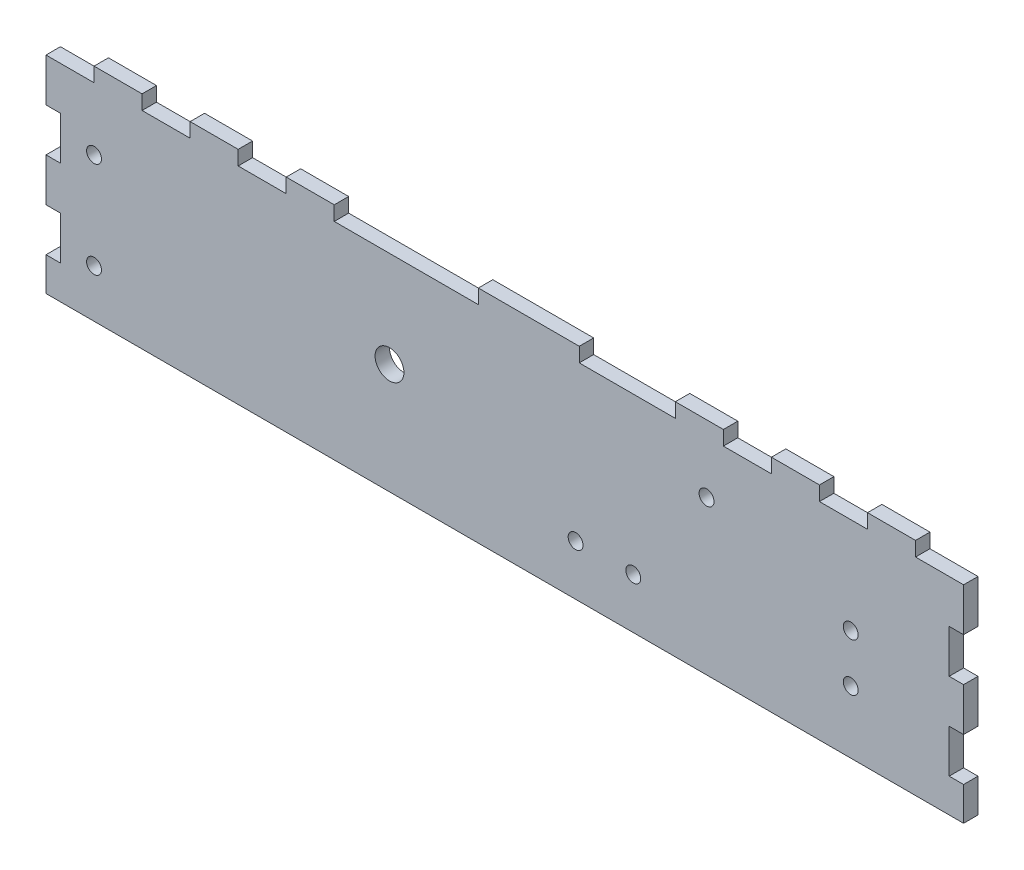
SolidWorks part; units mm, degrees
ref_plane "Front Plane" through (0, 0, 0) normal (0, 0, 1) x (1, 0, 0)
ref_plane "Top Plane" through (0, 0, 0) normal (0, 1, 0) x (1, 0, 0)
ref_plane "Right Plane" through (0, 0, 0) normal (1, 0, 0) x (0, 0, -1)
sketch "Sketch1" plane through (0, 0, 0) normal (0, 0, 1) x (1, 0, 0)
  line L4 (-191, 0) -> (0, 0)
  line L5 (0, 0) -> (0, 46)
  line L6 (0, 46) -> (-191, 46)
  line L7 (-191, 46) -> (-191, 0)
  line L8 (-191, 0) -> (0, 0)
  line L9 (0, 0) -> (0, 46)
  line L10 (0, 46) -> (-191, 46)
  line L11 (-191, 46) -> (-191, 0)
  circle A0 centre (-181, 30) radius 1.55 construction
  circle A1 centre (-181, 10) radius 1.55 construction
  circle A2 centre (-181, 30) radius 1.55
  circle A3 centre (-181, 10) radius 1.55
  dimension "D1" = 0
extrude "Boss-Extrude1" add sketch "Sketch1" along normal blind 3
sketch "Sketch5" plane through (0, 0, 3) normal (0, 0, 1) x (1, 0, 0)
  line L0 (-95.5, 0) -> (-95.5, 46) construction
  line L1 (-191, 0) -> (0, 0) construction
  line L2 (0, 46) -> (-191, 46) construction
ref_axis "Axis1" through (-95.5, 0, 3) along (0, 1, 0)
ref_plane "Plane1" through (-95.5, 0, 0) normal (1, 0, 0) x (0, 1, 0)
sketch "Sketch2" plane through (0, 0, 3) normal (0, 0, 1) x (1, 0, 0)
  line L0 (-119.5, 46) -> (-119.5, 0) construction
  line L1 (-119.5, 46) -> (-119.5, 0)
  point P2 (-119.5, 23)
ref_point "MointPoint-Sus"
sketch "Sketch3" plane through (0, 0, 0) normal (0, 0, -1) x (-1, 0, 0)
  line L4 (50, 43) -> (50, 46)
  line L5 (50, 46) -> (40, 46)
  line L6 (40, 46) -> (40, 43)
  line L7 (40, 43) -> (50, 43)
  line L8 (50, 43) -> (50, 46)
  line L9 (50, 46) -> (40, 46)
  line L10 (40, 46) -> (40, 43)
  line L11 (40, 43) -> (50, 43)
  line L12 (30, 43) -> (30, 46)
  line L13 (30, 46) -> (20, 46)
  line L14 (20, 46) -> (20, 43)
  line L15 (20, 43) -> (30, 43)
  line L16 (30, 43) -> (30, 46)
  line L17 (30, 46) -> (20, 46)
  line L18 (20, 46) -> (20, 43)
  line L19 (20, 43) -> (30, 43)
  line L20 (10, 43) -> (10, 46)
  line L21 (10, 46) -> (0, 46)
  line L22 (0, 46) -> (0, 43)
  line L23 (0, 43) -> (10, 43)
  line L24 (10, 43) -> (10, 46)
  line L25 (10, 46) -> (0, 46)
  line L26 (0, 46) -> (0, 43)
  line L27 (0, 43) -> (10, 43)
  line L28 (171, 43) -> (171, 46)
  line L29 (171, 46) -> (161, 46)
  line L30 (161, 46) -> (161, 43)
  line L31 (161, 43) -> (171, 43)
  line L32 (171, 43) -> (171, 46)
  line L33 (171, 46) -> (161, 46)
  line L34 (161, 46) -> (161, 43)
  line L35 (161, 43) -> (171, 43)
  line L36 (151, 43) -> (151, 46)
  line L37 (151, 46) -> (141, 46)
  line L38 (141, 46) -> (141, 43)
  line L39 (141, 43) -> (151, 43)
  line L40 (151, 43) -> (151, 46)
  line L41 (151, 46) -> (141, 46)
  line L42 (141, 46) -> (141, 43)
  line L43 (141, 43) -> (151, 43)
  line L44 (131, 46) -> (101, 46)
  line L45 (101, 46) -> (101, 43)
  line L46 (101, 43) -> (131, 43)
  line L47 (131, 43) -> (131, 46)
  line L48 (131, 46) -> (101, 46)
  line L49 (101, 46) -> (101, 43)
  line L50 (101, 43) -> (131, 43)
  line L51 (131, 43) -> (131, 46)
  line L52 (80, 46) -> (60, 46)
  line L53 (80, 43) -> (80, 46)
  line L54 (60, 43) -> (80, 43)
  line L55 (60, 46) -> (60, 43)
  line L56 (80, 46) -> (60, 46)
  line L57 (80, 43) -> (80, 46)
  line L58 (60, 43) -> (80, 43)
  line L59 (60, 46) -> (60, 43)
  line L60 (181, 43) -> (191, 43)
  line L61 (181, 46) -> (181, 43)
  line L62 (191, 46) -> (181, 46)
  line L63 (191, 43) -> (191, 46)
  line L64 (181, 43) -> (191, 43)
  line L65 (181, 46) -> (181, 43)
  line L66 (191, 46) -> (181, 46)
  line L67 (191, 43) -> (191, 46)
  dimension "D1" = 0
  dimension "D2" = 0
  dimension "D3" = 0
  dimension "D4" = 0
  dimension "D5" = 0
  dimension "D6" = 0
  dimension "D7" = 0
  dimension "D8" = 0
extrude "Cut-Extrude1" cut sketch "Sketch3" against normal up to next
sketch "Sketch4" plane through (0, 0, 3) normal (0, 0, 1) x (1, 0, 0)
  line L0 (-3, 43) -> (-3, 0) construction
  line L1 (0, 43) -> (-10, 43) construction
  line L2 (-191, 0) -> (0, 0) construction
  line L3 (0, 0) -> (0, 43) construction
  line L4 (-3, 34) -> (0, 34)
  line L5 (-3, 25) -> (0, 25)
  line L6 (-3, 16) -> (0, 16)
  line L7 (-3, 7) -> (0, 7)
  line L8 (0, 34) -> (0, 25)
  line L9 (-3, 25) -> (-3, 34)
  line L10 (0, 16) -> (0, 7)
  line L11 (-3, 7) -> (-3, 16)
  dimension "D1" = 3
  dimension "D2" = 9
  dimension "D3" = 4
extrude "Cut-Extrude2" cut sketch "Sketch4" against normal up to next
mirror "Mirror1" about plane through (-95.5, 0, 0) normal (1, 0, 0) of "Cut-Extrude2"
sketch "Sketch6" plane through (0, 0, 3) normal (0, 0, 1) x (1, 0, 0)
  circle A0 centre (-119.5, 23) radius 3
  point P0 (-119.5, 23)
  dimension "D1" = 6
extrude "Cut-Extrude3" cut sketch "Sketch6" against normal up to next
sketch "Sketch7" plane through (0, 0, 3) normal (0, 0, 1) x (1, 0, 0)
  circle A0 centre (-53.5, 32) radius 1.55 construction
  circle A1 centre (-68.7574, 10.5) radius 1.55 construction
  circle A2 centre (-80.7574, 10.5) radius 1.55 construction
  circle A3 centre (-23.5, 23) radius 1.55 construction
  circle A4 centre (-23.5, 13) radius 1.55 construction
  circle A5 centre (-53.5, 32) radius 1.55
  circle A6 centre (-68.7574, 10.5) radius 1.55
  circle A7 centre (-80.7574, 10.5) radius 1.55
  circle A8 centre (-23.5, 23) radius 1.55
  circle A9 centre (-23.5, 13) radius 1.55
extrude "Cut-Extrude4" cut sketch "Sketch7" against normal up to next
